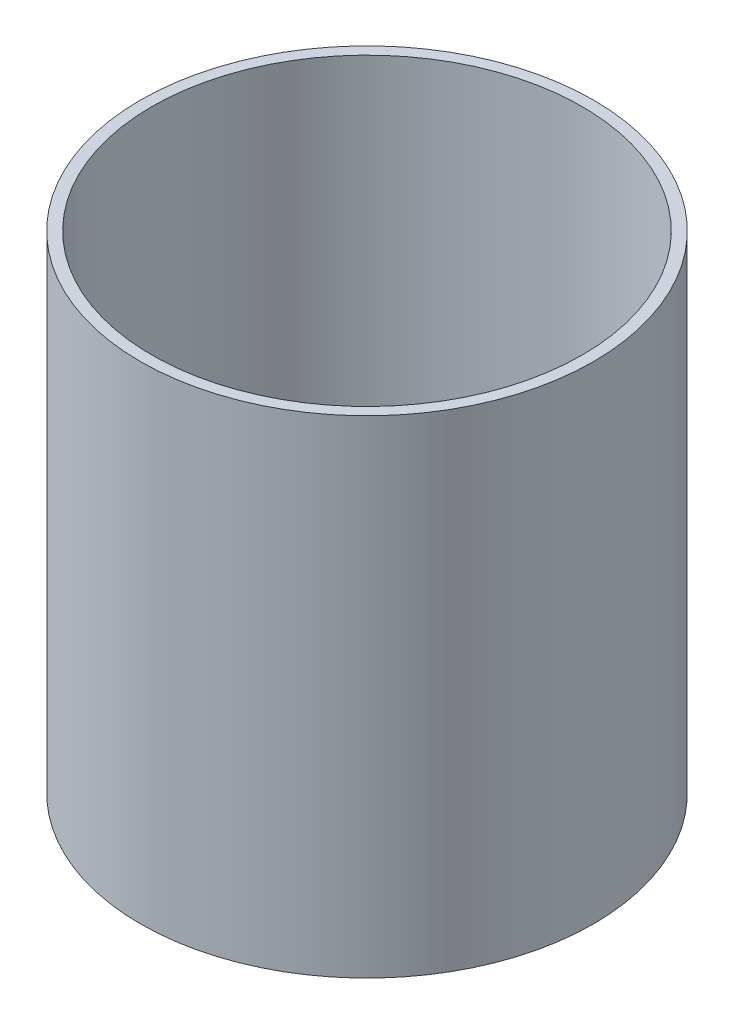
SolidWorks part; units mm, degrees
ref_plane "Front Plane" through (0, 0, 0) normal (0, 0, 1) x (1, 0, 0)
ref_plane "Top Plane" through (0, 0, 0) normal (0, 1, 0) x (1, 0, 0)
ref_plane "Right Plane" through (0, 0, 0) normal (1, 0, 0) x (0, 0, -1)
sketch "Sketch1" plane through (0, 0, 0) normal (0, 1, 0) x (1, 0, 0)
  circle A0 centre (0, 0) radius 60
  dimension "D1" = 120
extrude "Extrude-Thin1" add sketch "Sketch1" along normal blind 129 thin thin type one direction reverse wall 3
